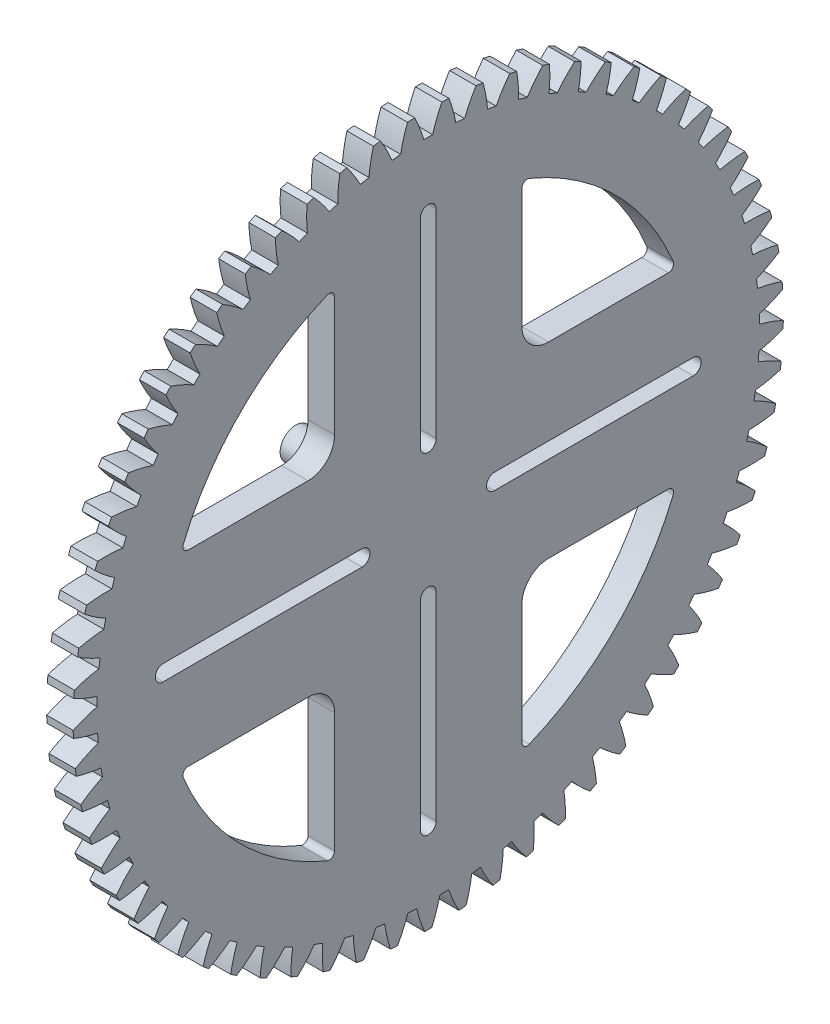
SolidWorks part; units mm, degrees
material "ABS"
ref_plane "Plane1" through (0, 0, 0) normal (0, 0, 1) x (1, 0, 0)
ref_plane "Plane2" through (0, 0, 0) normal (0, 1, 0) x (1, 0, 0)
ref_plane "Plane3" through (0, 0, 0) normal (1, 0, 0) x (0, 0, -1)
sketch "HoldingSke" plane through (0, 0, 0) normal (0, 1, 0) x (1, 0, 0)
  line L0 (0, 0) -> (0.1057, -0.2266)
  line L1 (-15, 0) -> (100, 0) construction
  line L2 (0, 0) -> (-2.1039, 2.3779)
  line L3 (0, 0) -> (-11.863, 4.5341)
  line L4 (0, 0) -> (3.6497, 7.8269)
  line L5 (0, 0) -> (-46.8476, -17.4728)
  line L6 (0, 0) -> (-8.2896, -5.593)
  line L7 (-2.1039, 2.3779) -> (8.6586, 51.2059)
  line L8 (-76.2, 54.61) -> (-74.8, 54.61)
  line L9 (-71.009, 38.7566) -> (-53.1078, 45.2721)
  line L10 (-76.2, 71.12) -> (104.1128, 71.12)
  line L11 (0, 0) -> (-10, 0)
  line L12 (-76.2, 101.6) -> (-76.073, 101.6)
  line L13 (24.9733, 27.94) -> (52.9518, 28.4284)
  line L14 (24.9733, 27.94) -> (24.9743, 27.94)
  line L15 (24.9733, 27.94) -> (100.4006, 29.5858)
  line L16 (-63.627, -4) -> (-12.827, -4)
  circle A0 centre (0, 0) radius 4
  circle A1 centre (0, 0) radius 6
  circle A2 centre (0, 0) radius 6
  circle A3 centre (0, 0) radius 4
  dimension "Num_teeth" = 65
  dimension "Pitch_radius" = 180.3128
  dimension "Width" = 10
  dimension "Thickness" = 10
sketch "BasProSke" plane through (0, 0, 0) normal (0, 1, 0) x (1, 0, 0)
  line L0 (-10, 0) -> (60, 0) construction
  line L1 (0, 0) -> (0, 134)
  line L2 (0, 0) -> (10, 0)
  line L3 (10, 0) -> (10, 134)
  line L4 (10, 134) -> (0, 134)
  dimension "Thickness" = 10
  dimension "Diameter" = 268
revolve "Base-Revolve" add sketch "BasProSke" angle 360 about L0
sketch "TooCutSke" plane through (0, 0, 0) normal (1, 0, 0) x (0, 0, -1)
  line L1 (0, 0) -> (0, 107) construction
  line L2 (0, 0) -> (-3.3635, 129.9565) construction
  line L3 (0, 0) -> (-12.5583, 259.6309) construction
  line L4 (-3.3635, 129.9565) -> (-6.2792, 129.8155) construction
  arc A0 (1.6677, 124.9879) -> (-1.6677, 124.9879) centre (0, 0) ccw
  arc A1 (5.1425, 133.9267) -> (-5.1425, 133.9267) centre (0, 0) ccw
  circle A2 centre (0, 0) radius 130 construction
  circle A3 centre (0, 0) radius 122.16 construction
  arc A4 (-1.6677, 124.9879) -> (-5.1425, 133.9267) centre (-51.6653, 110.6968) ccw
  arc A5 (5.1425, 133.9267) -> (1.6677, 124.9879) centre (51.6653, 110.6968) ccw
extrude "ToothCut" cut sketch "TooCutSke" along normal through all
fillet "Breaks" [suppressed] radius 0.08
fillet "RootFillets" [suppressed] radius 1.001
pattern_circular "TeethCuts" count 65 every 5.538 about axis through (-10, 0, 0) along (1, 0, 0) of "ToothCut", "RootFillets", "Breaks"
sketch "HubNeaOneSke" plane through (0, 0, 0) normal (-1, 0, 0) x (0, 0, 1)
  circle A0 centre (0, 0) radius 6
  dimension "Diameter" = 12
extrude "HubNearOne" add sketch "HubNeaOneSke" along normal blind 40.0001
sketch "HubNeaBotSke" plane through (0, 0, 0) normal (-1, 0, 0) x (0, 0, 1)
  circle A0 centre (0, 0) radius 6
  dimension "Diameter" = 12
extrude "HubNearBoth" [suppressed] add sketch "HubNeaBotSke" along normal blind 20
ref_plane "FarPln" through (10, 0, 0) normal (1, 0, 0) x (0, 0, -1)
sketch "HubFarSke" plane through (10, 0, 0) normal (1, 0, 0) x (0, 0, -1)
  circle A0 centre (0, 0) radius 6
  dimension "Diameter" = 12
extrude "HubFar" [suppressed] add sketch "HubFarSke" along normal blind 20
sketch "BorSke" plane through (0, 0, 0) normal (1, 0, 0) x (0, 0, -1)
  circle A0 centre (0, 0) radius 4
  dimension "Diameter" = 8
extrude "Bore" cut sketch "BorSke" along normal mid plane 100.0001
sketch "KeySke" plane through (0, 0, 0) normal (1, 0, 0) x (0, 0, -1)
  line L0 (-1.5, 0) -> (-1.5, 5.4)
  line L1 (-1.5, 5.4) -> (1.5, 5.4)
  line L2 (1.5, 5.4) -> (1.5, 0)
  line L3 (0, 0) -> (0, 34) construction
  line L4 (-1.5, 0) -> (1.5, 0)
  dimension "Width" = 3
extrude "Keyway" [suppressed] cut sketch "KeySke" along normal mid plane 100.0001
pattern_circular "Keyway2" [suppressed] count 2 every 90 about axis through (-10, 0, 0) along (1, 0, 0)
sketch "Esquisse1" plane through (10, 0, 0) normal (1, 0, 0) x (0, 0, -1)
  line L0 (0, 0) -> (0, 125) construction
  line L1 (100, 3) -> (25, 3)
  line L2 (100, -3) -> (25, -3)
  line L3 (-3, 100) -> (-3, 25)
  line L4 (-3, 25) -> (3, 25)
  line L5 (3, 100) -> (3, 25)
  line L6 (-3, 100) -> (3, 25) construction
  line L7 (-3, 25) -> (3, 100) construction
  line L8 (3, -100) -> (3, -25)
  line L9 (-3, -100) -> (-3, -25)
  line L10 (-100, -3) -> (-25, -3)
  line L11 (-100, 3) -> (-25, 3)
  arc A0 (-3, 25) -> (3, 25) centre (0, 25) ccw
  arc A1 (3, 100) -> (-3, 100) centre (0, 100) ccw
  arc A2 (100, -3) -> (100, 3) centre (100, 0) ccw
  arc A3 (25, 3) -> (25, -3) centre (25, 0) ccw
  arc A4 (-3, -100) -> (3, -100) centre (0, -100) ccw
  arc A5 (3, -25) -> (-3, -25) centre (0, -25) ccw
  arc A6 (-100, 3) -> (-100, -3) centre (-100, 0) ccw
  arc A7 (-25, -3) -> (-25, 3) centre (-25, 0) ccw
  point P3 (0, 62.5)
  point P35 (0, 0)
  dimension "D1" = 25
  dimension "D2" = 75
  dimension "D3" = 6
  dimension "D4" = 4
extrude "Enlèv. mat.-Extru.1" cut sketch "Esquisse1" against normal blind 10 contours L5 A1 L3 L4 | L4 A0 | L1 A3 L2 A2 | L10 A7 L11 A6 | L8 A5 L9 A4
sketch "Esquisse3" plane through (0, 0, 0) normal (-1, 0, 0) x (0, 0, 1)
  line L0 (0, 0) -> (-113, 0) construction
  line L1 (-113, 0) -> (-113, 8) construction
  line L2 (-113, -8) -> (-113, -18)
  line L3 (-113, 8) -> (-12, 8)
  line L4 (-113, 8) -> (-113, 18)
  line L5 (-113, 18) -> (-18, 18)
  line L6 (-12, 8) -> (-12, 12)
  line L7 (-12, -8) -> (-12, -12)
  line L8 (-113, -8) -> (-12, -8)
  line L9 (-113, -18) -> (-18, -18)
  line L10 (8, 113) -> (8, 12)
  line L11 (18, 113) -> (18, 18)
  line L12 (8, 12) -> (12, 12)
  line L13 (8, 113) -> (18, 113)
  line L14 (-8, 113) -> (-8, 12)
  line L15 (-8, 113) -> (-18, 113)
  line L16 (-18, 113) -> (-18, 18)
  line L17 (-8, 12) -> (-12, 12)
  line L18 (113, -8) -> (12, -8)
  line L19 (113, -18) -> (18, -18)
  line L20 (12, -8) -> (12, -12)
  line L21 (113, -8) -> (113, -18)
  line L22 (113, 8) -> (12, 8)
  line L23 (113, 8) -> (113, 18)
  line L24 (113, 18) -> (18, 18)
  line L25 (12, 8) -> (12, 12)
  line L26 (-8, -113) -> (-8, -12)
  line L27 (-18, -113) -> (-18, -18)
  line L28 (-8, -12) -> (-12, -12)
  line L29 (-8, -113) -> (-18, -113)
  line L30 (8, -113) -> (8, -12)
  line L31 (8, -113) -> (18, -113)
  line L32 (18, -113) -> (18, -18)
  line L33 (8, -12) -> (12, -12)
  point P38 (0, 0)
  dimension "D1" = 113
  dimension "D2" = 8
  dimension "D4" = 10
  dimension "D5" = 4
extrude "Enlèv. mat.-Extru.2" cut sketch "Esquisse3" against normal blind 5
fillet "Congé1" radius 10 8 edges at (2.5, -18, -18) (2.5, 18, -18) (2.5, 18, 18) (2.5, -18, 18) (2.5, -12, 12) (2.5, -12, -12) (2.5, 12, 12) (2.5, 12, -12)
fillet "Congé2" radius 2 16 edges at (2.5, 113, -18) (2.5, 113, -8) (2.5, 113, 8) (2.5, 113, 18) (2.5, 18, 113) (2.5, 8, 113) (2.5, -8, 113) (2.5, -18, 113) (2.5, -113, 18) (2.5, -113, 8) (2.5, -113, -8) (2.5, -113, -18) (2.5, -18, -113) (2.5, -8, -113) (2.5, 8, -113) (2.5, 18, -113)
sketch "Esquisse4" plane through (0, 0, 0) normal (-1, 0, 0) x (0, 0, 1)
  line L0 (0, 0) -> (35.3553, 35.3553) construction
  line L1 (35.3553, 35.3553) -> (35.3553, 93.5414)
  line L2 (35.3553, 35.3553) -> (93.5414, 35.3553)
  line L3 (35.3553, -35.3553) -> (93.5414, -35.3553)
  line L4 (35.3553, -35.3553) -> (35.3553, -93.5414)
  line L5 (-35.3553, -35.3553) -> (-35.3553, -93.5414)
  line L6 (-35.3553, -35.3553) -> (-93.5414, -35.3553)
  line L7 (-35.3553, 35.3553) -> (-93.5414, 35.3553)
  line L8 (-35.3553, 35.3553) -> (-35.3553, 93.5414)
  arc A0 (35.3553, 93.5414) -> (93.7151, 34.8925) centre (0, 0) cw
  arc A1 (93.5414, -35.3553) -> (34.8925, -93.7151) centre (0, 0) cw
  arc A2 (-35.3553, -93.5414) -> (-93.7151, -34.8925) centre (0, 0) cw
  arc A3 (-93.5414, 35.3553) -> (-34.8925, 93.7151) centre (0, 0) cw
  point P21 (0, 0)
  dimension "D2" = 4
  dimension "D1" = 50
extrude "Enlèv. mat.-Extru.3" cut sketch "Esquisse4" against normal through all contours A3 L7 L8 | A0 L1 L2 | A1 L3 L4 | A2 L5 L6
fillet "Congé3" radius 10 4 edges at (5, -35.3553, -35.3553) (5, -35.3553, 35.3553) (5, 35.3553, 35.3553) (5, 35.3553, -35.3553)
fillet "Congé4" radius 2 8 edges at (5, -35.3553, -93.5414) (5, -93.5414, -35.3553) (5, -93.5414, 35.3553) (5, -35.3553, 93.5414) (5, 35.3553, 93.5414) (5, 93.5414, 35.3553) (5, 35.3553, -93.5414) (5, 93.5414, -35.3553)
fillet "Congé5" radius 1 48 edges at (0, 8, 61.5) (0, 8.5858, 112.4142) (0, 13, 113) (0, 17.4142, 112.4142) (0, 61.5, 8) (0, 112.4142, 8.5858) (0, 113, 13) (0, 112.4142, 17.4142) (0, 69.5, 18) (0, 20.9289, 20.9289) (0, -61.5, 8) (0, -112.4142, 8.5858) (0, -113, 13) (0, -112.4142, 17.4142) (0, -8, 61.5) (0, -8.5858, 112.4142) (0, -13, 113) (0, -17.4142, 112.4142) (0, -18, 69.5) (0, -20.9289, 20.9289) (0, -61.5, -8) (0, -112.4142, -8.5858) (0, -113, -13) (0, -112.4142, -17.4142) (0, -69.5, -18) (0, -20.9289, -20.9289) (0, -18, -69.5) (0, -17.4142, -112.4142) (0, -13, -113) (0, -8.5858, -112.4142) (0, 61.5, -8) (0, 112.4142, -8.5858) (0, 113, -13) (0, 112.4142, -17.4142) (0, 69.5, -18) (0, 20.9289, -20.9289) (0, 8, -61.5) (0, 8.5858, -112.4142) (0, 13, -113) (0, 17.4142, -112.4142) (0, 10.2887, 10.2887) (0, -10.2887, 10.2887) (0, 18, 69.5) (0, -69.5, 18) (0, -10.2887, -10.2887) (0, -8, -61.5) (0, 10.2887, -10.2887) (0, 18, -69.5)
sketch "Esquisse5" plane through (0, 0, 0) normal (-1, 0, 0) x (0, 0, 1)
  circle A0 centre (0, 0) radius 11
  circle A1 centre (0, 0) radius 6
  dimension "D1" = 22
extrude "Boss.-Extru.1" add sketch "Esquisse5" along normal blind 17
fillet "Congé6" radius 2 1 edges at (0, 0, -11)
sketch "Esquisse6" plane through (-40.0001, 0, 0) normal (-1, 0, 0) x (0, 0, 1)
  line L0 (0, 0) -> (0, 3) construction
  line L1 (-2.6458, 3) -> (2.6458, 3)
  arc A1 (-2.6458, 3) -> (2.6458, 3) centre (0, 0) cw
  point P8 (0, 3)
  circle M2 centre (0, 0) radius 4
  dimension "D1" = 3
extrude "Boss.-Extru.2" add sketch "Esquisse6" against normal blind 30 contours L1 M2
sketch "Esquisse7" plane through (-10.0001, 0, 0) normal (1, 0, 0) x (0, 0, -1)
  circle A0 centre (0, 0) radius 4
extrude "Boss.-Extru.3" add sketch "Esquisse7" along normal up to surface (20.0001 mm away) up to face at (10, -56.8058, 56.8058)
sketch "Esquisse8" plane through (-40.0001, 0, 0) normal (-1, 0, 0) x (0, 0, 1)
  circle A0 centre (0, 0) radius 5.9
  circle A1 centre (0, 0) radius 6
  dimension "D1" = 11.8
  dimension "D2" = 12
extrude "Enlèv. mat.-Extru.4" cut sketch "Esquisse8" against normal blind 23
equation "' \"Module@HoldingSke\" = 6.35"
equation "' \"Num_teeth@HoldingSke\" = 12"
equation "' \"Ap@HoldingSke\" =  20"
equation "' \"Ap@HoldingSke\" = 20"
equation "' \"Width@HoldingSke\" = 0.5 * 25.4"
equation "' \"Hub_dia@HoldingSke\"= 1 * 25.4"
equation "' \"Hub_dia@HoldingSke\" = 1 * 25.4"
equation "' \"Overall_len@HoldingSke\" = 1.0 * 25.4"
equation "' \"Bore@HoldingSke\" = 0.75 * 25.4"
equation "' \"T_dim@HoldingSke\" = 0.1 * 25.4"
equation "' \"Width@KeySke\" = 0.25 * 25.4"
equation "' \"Show_teeth@HoldingSke\" = 13"
equation "' \"Backlash@HoldingSke\" = 0.009 * 25.4"
equation "' \"Addendum_fac@HoldingSke\" = 1.0"
equation "' \"Dedendum_fac@HoldingSke\" = 1.25"
equation "' \"Dedendum_add@HoldingSke\" = 0.00005 * 25.4"
equation "' \"Clearance_fac@HoldingSke\" = 0.25"
equation "\"Pitch@HoldingSke\" = 1 / \"Module@HoldingSke\""
equation "\"Overcut_dia@TooCutSke\" = (\"Num_teeth@HoldingSke\" + 2 * \"Addendum_fac@HoldingSke\") / \"Pitch@HoldingSke\" + 0.002 * 25.4"
equation "\"Pitch_dia@TooCutSke\" = \"Num_teeth@HoldingSke\" / \"Pitch@HoldingSke\""
equation "\"Base_dia@TooCutSke\" = \"Num_teeth@HoldingSke\" / \"Pitch@HoldingSke\" * cos((\"Ap@HoldingSke\"  * 3.14159265 / 180))"
equation "\"Root_dia@TooCutSke\" = (\"Num_teeth@HoldingSke\" + 2) / \"Pitch@HoldingSke\" - 2 * (\"Addendum_fac@HoldingSke\" + \"Dedendum_fac@HoldingSke\") / \"Pitch@HoldingSke\" - \"Dedendum_add@HoldingSke\" * 2"
equation "\"Half_ang@TooCutSke\" = 180 / \"Num_teeth@HoldingSke\""
equation "\"Half_CT@TooCutSke\" = \"Num_teeth@HoldingSke\" / \"Pitch@HoldingSke\" * sin((3.14159265 / 2 / \"Num_teeth@HoldingSke\")) / 2 - 7 * \"Backlash@HoldingSke\" / 4"
equation "\"Flank_rad@TooCutSke\" = \"Num_teeth@HoldingSke\" / \"Pitch@HoldingSke\" / 5"
equation "\"Radius@RootFillets\" = \"Clearance_fac@HoldingSke\" / \"Pitch@HoldingSke\" + \"Dedendum_add@HoldingSke\""
equation "\"Break_rad@Breaks\" = 0.02 / \"Pitch@HoldingSke\""
equation "\"Thickness@HoldingSke\" = \"Width@HoldingSke\""
equation "\"OAL@HoldingSke\" = \"Thickness@HoldingSke\""
equation "\"MHD@HoldingSke\" = (\"Num_teeth@HoldingSke\" + 2) / \"Pitch@HoldingSke\" - 2 * (\"Addendum_fac@HoldingSke\" + \"Dedendum_fac@HoldingSke\")  / \"Pitch@HoldingSke\" - \"Dedendum_add@HoldingSke\" * 2"
equation "\"MBD@HoldingSke\" = (\"Num_teeth@HoldingSke\" + 2) / \"Pitch@HoldingSke\" - 2 * (\"Addendum_fac@HoldingSke\" + \"Dedendum_fac@HoldingSke\")  / \"Pitch@HoldingSke\" - \"Dedendum_add@HoldingSke\" * 2 - 0.002 * 25.4"
equation "\"MHD@HoldingSke\" = ((sgn( \"MHD@HoldingSke\" - \"Hub_dia@HoldingSke\" )-1)*( \"MHD@HoldingSke\" - \"Hub_dia@HoldingSke\" ))/-2+ \"Hub_dia@HoldingSke\""
equation "\"MBD@HoldingSke\" = ((sgn( \"MBD@HoldingSke\" - \"Bore@HoldingSke\" )-1)*( \"MBD@HoldingSke\" - \"Bore@HoldingSke\" ))/-2+ \"Bore@HoldingSke\""
equation "\"OAL@HoldingSke\" = ((sgn( \"OAL@HoldingSke\" - \"Overall_len@HoldingSke\" )+1)*( \"OAL@HoldingSke\" - \"Overall_len@HoldingSke\" ))/2 + \"Overall_len@HoldingSke\" + 0.000002 * 25.4"
equation "\"Num_teeth@TeethCuts\" = int( \"Show_teeth@HoldingSke\" ) + 1"
equation "\"Num_teeth@TeethCuts\" = ((sgn( \"Num_teeth@TeethCuts\" - \"Num_teeth@HoldingSke\" )-1)*( \"Num_teeth@TeethCuts\" - \"Num_teeth@HoldingSke\" ))/-2+ \"Num_teeth@HoldingSke\""
equation "\"Num_teeth@TeethCuts\" = ((sgn( \"Num_teeth@TeethCuts\" - 2.0)+1)*( \"Num_teeth@TeethCuts\" - 2.0))/2 +2.0"
equation "\"Angle@TeethCuts\" = 360.0 / \"Num_teeth@HoldingSke\""
equation "\"Diameter@BasProSke\" = (\"Num_teeth@HoldingSke\" + 2 * \"Addendum_fac@HoldingSke\") / \"Pitch@HoldingSke\""
equation "\"Thickness@BasProSke\"  = \"Thickness@HoldingSke\""
equation "' \"Fillet_rad@BasProSke\" =  \"Thickness@HoldingSke\" * 0.05"
equation "' \"Fillet_rad@BasProSke\" = \"Thickness@HoldingSke\" * 0.05"
equation "\"MHD@HoldingSke\" = ((sgn( \"MHD@HoldingSke\" - \"Root_dia@TooCutSke\" )-1)*( \"MHD@HoldingSke\" - \"Root_dia@TooCutSke\" ))/-2+ \"Root_dia@TooCutSke\""
equation "\"Diameter@HubNeaOneSke\" = \"MHD@HoldingSke\""
equation "\"Length@HubNearOne\" = \"OAL@HoldingSke\" - \"Thickness@BasProSke\""
equation "\"Diameter@HubNeaBotSke\" = \"MHD@HoldingSke\""
equation "\"Length@HubNearBoth\" = ( \"OAL@HoldingSke\" - \"Thickness@BasProSke\" ) / 2.0"
equation "\"Thickness@FarPln\" = \"Thickness@BasProSke\""
equation "\"Diameter@HubFarSke\" = \"MHD@HoldingSke\""
equation "\"Length@HubFar\" = ( \"OAL@HoldingSke\" - \"Thickness@BasProSke\" ) / 2.0"
equation "\"Diameter@BorSke\" = \"MBD@HoldingSke\""
equation "\"D1@Bore\" = \"OAL@HoldingSke\" * 2.0"
equation "\"D1@Keyway\" = \"OAL@HoldingSke\" * 2.0"
equation "\"Offset@KeySke\" = \"T_dim@HoldingSke\" + \"MBD@HoldingSke\" / 2.0"
